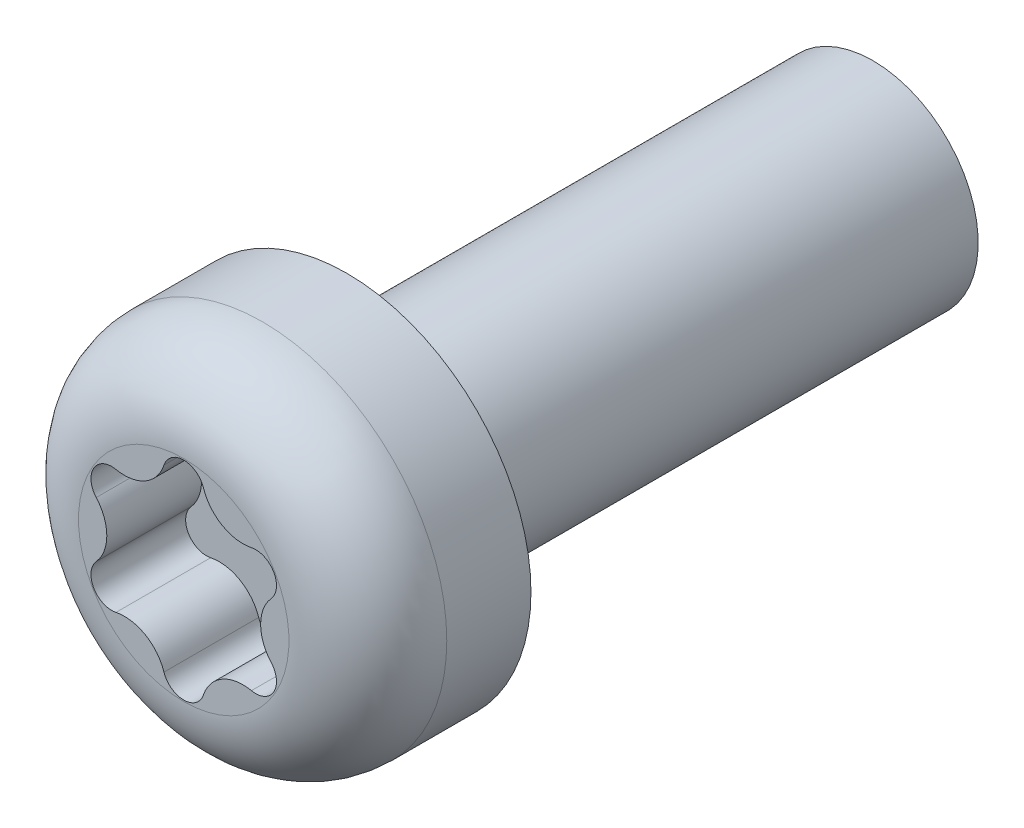
SolidWorks part; units mm, degrees
material "Alloy Steel"
ref_plane "Front Plane" through (0, 0, 0) normal (0, 0, 1) x (1, 0, 0)
ref_plane "Top Plane" through (0, 0, 0) normal (0, 1, 0) x (1, 0, 0)
ref_plane "Right Plane" through (0, 0, 0) normal (1, 0, 0) x (0, 0, -1)
ref_axis "Axis1" through (0, 0, -52.8182) along (0, 0, 1)
ref_axis "Axis2" through (0, -15.5981, 0) along (0, 1, 0)
ref_axis "Axis3" through (-12.2581, 0, 0) along (1, 0, 0)
sketch "Sketch1" plane through (0, 0, 0) normal (1, 0, 0) x (0, 0, -1)
  line L0 (-3.1, 0) -> (-3.1, 2)
  line L1 (-1.6, 3.5) -> (0, 3.5)
  line L2 (0, 3.5) -> (0, 2)
  line L3 (0, 2) -> (10, 2)
  line L4 (10, 2) -> (10, 0)
  line L5 (10, 0) -> (-3.1, 0)
  line L6 (-5.5849, 0) -> (13.8966, 0) construction
  arc A0 (-1.6, 3.5) -> (-3.1, 2) centre (-1.6, 2) ccw
  point P13 (0, 2)
  dimension "D1" = 4
  dimension "D2" = 7
  dimension "D3" = 3.1
  dimension "D4" = 4
  dimension "Length" = 10
revolve "Revolve1" add sketch "Sketch1" angle 360 about L6
cosmetic thread "Cosmetic Thread1" parameters "D1"=10, "D2"=2.439
sketch "Sketch2" plane through (0, 0, 3.1) normal (0, 0, 1) x (1, 0, 0)
  line L0 (0, 0) -> (0, 1.975) construction
  line L1 (-0.7308, 1.2658) -> (0, 0)
  line L2 (0, 0) -> (0.7308, 1.2658)
  arc A0 (-0.7308, 1.2658) -> (-0.3753, 1.7033) centre (-1.1258, 1.9499) ccw
  arc A1 (-0.3753, 1.7033) -> (0.3753, 1.7033) centre (0, 1.58) cw
  arc A2 (0.3753, 1.7033) -> (0.7308, 1.2658) centre (1.1258, 1.9499) ccw
  circle A3 centre (0, 0) radius 1.975 construction
  dimension "D1" = 3.95
  dimension "D3" = 0.395
  dimension "D4" = 0.79
  dimension "D2" = 60
extrude "Cut-Extrude1" cut sketch "Sketch2" against normal blind 1.8
pattern_circular "CirPattern1" count 6 over 360 about axis through (0, 0, 5.5849) along (0, 0, 1) of "Cut-Extrude1"
equation "\"D3@Sketch2\"=\"D1@Sketch2\"*.1"
equation "\"D4@Sketch2\"=\"D3@Sketch2\"*2"
